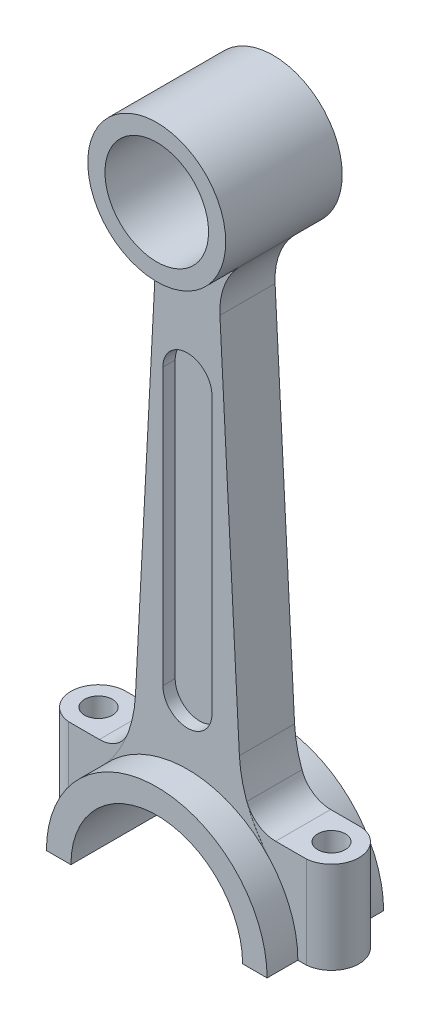
SolidWorks part; units mm, degrees
ref_plane "Front Plane" through (0, 0, 0) normal (0, 0, 1) x (1, 0, 0)
ref_plane "Top Plane" through (0, 0, 0) normal (0, 1, 0) x (1, 0, 0)
ref_plane "Right Plane" through (0, 0, 0) normal (1, 0, 0) x (0, 0, -1)
sketch "Sketch1" plane through (0, 0, 0) normal (0, 0, 1) x (1, 0, 0)
  line L0 (0, 74.34) -> (0, -98.82) construction
  line L1 (-111.42, 0) -> (128.34, 0) construction
  line L2 (-10.6046, 68.9081) -> (-16.9576, -52.3141)
  line L3 (10.6046, 68.9081) -> (16.9576, -52.3141)
  line L4 (-36, -100.6) -> (-28, -100.6)
  line L5 (28, -100.6) -> (36, -100.6)
  arc A0 (16.5369, 85.3428) -> (-16.5369, 85.3428) centre (0, 100.6) ccw
  arc A1 (-26.9539, -76.7361) -> (-36, -100.6) centre (0, -100.6) ccw
  circle A2 centre (0, 100.6) radius 16.9
  arc A3 (28, -100.6) -> (-28, -100.6) centre (0, -100.6) ccw
  arc A4 (10.6046, 68.9081) -> (16.5369, 85.3428) centre (33.0738, 70.0856) cw
  arc A5 (-10.6046, 68.9081) -> (-16.5369, 85.3428) centre (-33.0738, 70.0856) ccw
  arc A6 (26.9539, -76.7361) -> (16.9576, -52.3141) centre (56.9028, -50.2207) cw
  arc A7 (-16.9576, -52.3141) -> (-26.9539, -76.7361) centre (-56.9028, -50.2207) cw
  arc A8 (36, -100.6) -> (26.9539, -76.7361) centre (0, -100.6) ccw
  point P15 (10, 80.4444)
  point P18 (-10, 80.4444)
  point P26 (0, -100.6)
  dimension "D1" = 45
  dimension "D2" = 33.8
  dimension "D5" = 72
  dimension "D6" = 56
  dimension "D8" = 22.5
  dimension "D9" = 40
  dimension "D3" = 201.2
  dimension "D4" = 100.6
  dimension "D7" = 6
extrude "Boss-Extrude1" add sketch "Sketch1" along normal mid plane 18
sketch "Sketch3" plane through (0, 0, 0) normal (0, 0, 1) x (1, 0, 0)
  line L0 (-28, -100.6) -> (-36, -100.6)
  line L1 (28, -100.6) -> (36, -100.6)
  arc A0 (28, -100.6) -> (-28, -100.6) centre (0, -100.6) ccw construction
  circle A1 centre (0, 100.6) radius 16.9 construction
  arc A2 (28, -100.6) -> (-28, -100.6) centre (0, -100.6) ccw
  circle A3 centre (0, 100.6) radius 16.9
  circle A4 centre (0, 100.6) radius 22.5
  arc A5 (36, -100.6) -> (-36, -100.6) centre (0, -100.6) ccw
extrude "Boss-Extrude2" add sketch "Sketch3" along normal mid plane 38
sketch "Sketch4" plane through (0, -100.6, 0) normal (0, -1, 0) x (1, 0, 0)
  line L0 (0, 30.9782) -> (0, -38.8936) construction
  line L1 (-55.6476, 0) -> (64.4446, 0) construction
  line L2 (-28, 8.9687) -> (28, 8.9687)
  line L4 (-28, -8.9687) -> (28, -8.9687)
  line L10 (-38.75, 8.9687) -> (-28, 8.9687)
  line L15 (-38.75, -8.9687) -> (-28, -8.9687)
  line L17 (38.75, -8.9687) -> (28, -8.9687)
  line L18 (38.75, 8.9687) -> (28, 8.9687)
  arc A0 (-38.75, 8.9687) -> (-38.75, -8.9687) centre (-38, 0) ccw
  arc A1 (38.75, -8.9687) -> (38.75, 8.9687) centre (38, 0) ccw
  circle A2 centre (38, 0) radius 4.5
  circle A3 centre (-38, 0) radius 4.5
  point P21 (36, -8.775)
  point P30 (-36, -8.775)
  dimension "D1" = 18
  dimension "D2" = 9
  dimension "D3" = 76
  dimension "D4" = 38
extrude "Boss-Extrude3" add sketch "Sketch4" against normal blind 30 contours A1 A2 | A0 A3 | A3 L1 A1 region at (0, -100.6, 0)
sketch "Sketch5" plane through (0, 0, 9) normal (0, 0, 1) x (1, 0, 0)
  line L0 (0, 100.6) -> (0, -120.7354) construction
  line L1 (-8, 45) -> (-8, -45)
  line L2 (8, 45) -> (8, -45)
  arc A0 (8, 45) -> (-8, 45) centre (0, 45) ccw
  arc A1 (-8, -45) -> (8, -45) centre (0, -45) ccw
  dimension "D1" = 16
  dimension "D2" = 16
  dimension "D3" = 90
  dimension "D4" = 45
extrude "Cut-Extrude2" cut sketch "Sketch5" against normal blind 4
mirror "Mirror1" about plane through (0, 0, 0) normal (0, 0, 1) of "Cut-Extrude2"
sketch "Sketch6" plane through (0, 0, 19) normal (0, 0, 1) x (1, 0, 0)
  line L0 (28, -100.6) -> (-28, -100.6) construction
  line L1 (28, -100.6) -> (-28, -100.6)
  arc A0 (28, -100.6) -> (-28, -100.6) centre (0, -100.6) ccw construction
  arc A1 (28, -100.6) -> (-28, -100.6) centre (0, -100.6) ccw
extrude "Cut-Extrude3" cut sketch "Sketch6" against normal through all
fillet "Fillet1" radius 10 1 edges at (22.4835, -70.6, 0)
fillet "Fillet2" radius 10 1 edges at (-22.4835, -70.6, 0)
sketch "Sketch7" plane through (0, -100.6, 0) normal (0, -1, 0) x (1, 0, 0)
  circle A0 centre (-38, 0) radius 4.5233
  circle A1 centre (38, 0) radius 4.5
extrude "Cut-Extrude4" cut sketch "Sketch7" against normal through all
